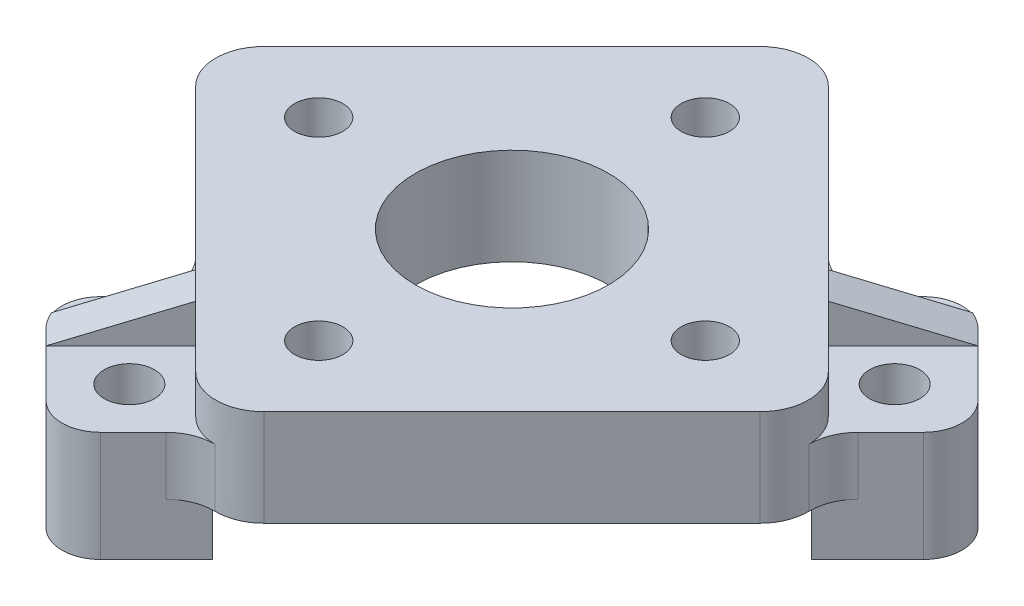
SolidWorks part; units mm, degrees
ref_plane "Front Plane" through (0, 0, 0) normal (0, 0, 1) x (1, 0, 0)
ref_plane "Top Plane" through (0, 0, 0) normal (0, 1, 0) x (1, 0, 0)
ref_plane "Right Plane" through (0, 0, 0) normal (1, 0, 0) x (0, 0, -1)
sketch "Sketch1" plane through (0, 0, 0) normal (0, 1, 0) x (1, 0, 0)
  line L0 (0, 10) -> (0, -10) construction
  line L1 (10, 0) -> (-10, 0) construction
  line L2 (0, 10) -> (10, 0) construction
  line L3 (10, 0) -> (0, -10) construction
  line L4 (0, -10) -> (-10, 0) construction
  line L8 (-10, 0) -> (0, 10) construction
  line L9 (1.7678, 14.5962) -> (14.5962, 1.7678)
  line L10 (14.5962, -1.7678) -> (1.7678, -14.5962)
  line L11 (-1.7678, -14.5962) -> (-14.5962, -1.7678)
  line L12 (-14.5962, 1.7678) -> (-1.7678, 14.5962)
  line L13 (16.364, 0) -> (0, -16.364) construction
  line L14 (0, -16.364) -> (-16.364, 0) construction
  line L15 (0, 16.364) -> (16.364, 0) construction
  line L16 (-16.364, 0) -> (0, 16.364) construction
  circle A7 centre (0, 10) radius 1.25
  circle A8 centre (0, -10) radius 1.25
  circle A9 centre (10, 0) radius 1.25
  circle A10 centre (-10, 0) radius 1.25
  circle A11 centre (0, 0) radius 5
  arc A12 (1.7678, -14.5962) -> (-1.7678, -14.5962) centre (0, -12.8284) cw
  arc A13 (14.5962, 1.7678) -> (14.5962, -1.7678) centre (12.8284, 0) cw
  arc A14 (-14.5962, -1.7678) -> (-14.5962, 1.7678) centre (-12.8284, 0) cw
  arc A15 (1.7678, 14.5962) -> (-1.7678, 14.5962) centre (0, 12.8284) ccw
  point P15 (0, 0)
  dimension "D2" = 2.5
  dimension "D3" = 10
  dimension "D4" = 4.5
  dimension "D5" = 2.5
  dimension "D1" = 20
extrude "Boss-Extrude1" add sketch "Sketch1" along normal blind 5
sketch "Sketch4" plane through (0, 0, 0) normal (0, -1, 0) x (1, 0, 0)
  circle A0 centre (0, 10) radius 3
  circle A1 centre (10, 0) radius 3
  circle A2 centre (-10, 0) radius 3
  circle A3 centre (0, -10) radius 3
  point P0 (0, 10)
  point P3 (10, 0)
  point P6 (-10, 0)
  point P9 (0, -10)
  dimension "D1" = 6
extrude "Cut-Extrude2" cut sketch "Sketch4" against normal blind 3
ref_plane "Plane1" through (0, -2.7, 0) normal (0, 1, 0) x (1, 0, 0)
ref_plane "Plane2" through (8.182, 0, 8.182) normal (0.7071, 0, 0.7071) x (0.7071, 0, -0.7071)
ref_plane "Plane3" through (2.5251, 0, 2.5251) normal (0.7071, 0, 0.7071) x (0.7071, 0, -0.7071)
sketch "Sketch3" plane through (0, -2.7, 0) normal (0, 1, 0) x (1, 0, 0)
  line L0 (-8.182, 8.182) -> (8.182, -8.182) construction
  line L1 (-1.7678, 14.5962) -> (-14.5962, 1.7678) construction
  line L2 (1.7678, -14.5962) -> (14.5962, -1.7678) construction
  line L3 (9.8995, 9.8995) -> (14.8492, 4.9497) construction
  line L5 (10.5375, 4.9497) -> (14.8492, 0.638)
  line L12 (14.5962, 1.7678) -> (1.7678, 14.5962) construction
  line L13 (14.8492, 0.638) -> (19.161, 4.9497)
  line L20 (0, 0) -> (9.8995, 9.8995) construction
  line L21 (14.5962, 1.7678) -> (1.7678, 14.5962) construction
  line L22 (19.161, 4.9497) -> (14.8492, 9.2615)
  line L23 (14.8492, 9.2615) -> (10.5375, 4.9497)
  line L24 (19.161, 4.9497) -> (10.5375, 4.9497) construction
  line L25 (-4.9497, -19.161) -> (-4.9497, -10.5375) construction
  line L26 (-9.8995, -9.8995) -> (-4.9497, -14.8492) construction
  line L27 (-9.2615, -14.8492) -> (-4.9497, -10.5375)
  line L28 (-4.9497, -19.161) -> (-9.2615, -14.8492)
  line L29 (-0.638, -14.8492) -> (-4.9497, -19.161)
  line L30 (-4.9497, -10.5375) -> (-0.638, -14.8492)
  line L31 (10.5375, 4.9497) -> (8.7697, 6.7175)
  line L32 (8.7697, 6.7175) -> (13.0815, 11.0293)
  line L33 (13.0815, 11.0293) -> (14.8492, 9.2615)
  line L34 (-4.9497, -10.5375) -> (-6.7175, -8.7697)
  line L35 (-6.7175, -8.7697) -> (-11.0293, -13.0815)
  line L36 (-11.0293, -13.0815) -> (-9.2615, -14.8492)
  circle A2 centre (14.8492, 4.9497) radius 1.3
  circle A3 centre (-4.9497, -14.8492) radius 1.3
  dimension "D1" = 2.6
  dimension "D2" = 7
  dimension "D3" = 3.0489
  dimension "D4" = 14
  dimension "D5" = 2.5
extrude "Boss-Extrude4" add sketch "Sketch3" along normal offset from surface (5.7 mm away) 3 contours L30 L27 L28 L29 A3 | L35 L36 L27 L34 | L22 L23 L5 L13 A2 | L33 L32 L31 L23 region at (12.7796, -2.7, -7.0194) region at (11.8095, -2.7, -7.9895) region at (-7.9895, -2.7, 11.8095) region at (-7.0194, -2.7, 12.7796) up to face at (0, 0, 7)
sketch "Sketch7" plane through (2.5251, 0, 2.5251) normal (0.7071, 0, 0.7071) x (0.7071, 0, -0.7071)
  line L0 (11.5711, 5) -> (17.0489, 3)
  line L1 (-11.5711, 5) -> (-17.0489, 3)
  line L2 (-17.0489, 3) -> (-11.5711, 3)
  line L3 (-11.5711, 3) -> (-11.5711, 5)
  line L4 (11.5711, 5) -> (11.5711, 3)
  line L5 (11.5711, 3) -> (17.0489, 3)
extrude "Boss-Extrude6" add sketch "Sketch7" along normal mid plane 2
fillet "Fillet1" radius 2.5 4 edges at (-7.1559, 1.5, 9.2081) (9.2081, 1.5, -7.1559) (15.1468, 1.5, -0.9355) (-0.9355, 1.5, 15.1468)
fillet "Fillet2" radius 2 4 edges at (-11.0293, 0.15, 13.0815) (-4.9497, 0.15, 19.161) (13.0815, 0.15, -11.0293) (19.161, 0.15, -4.9497)
